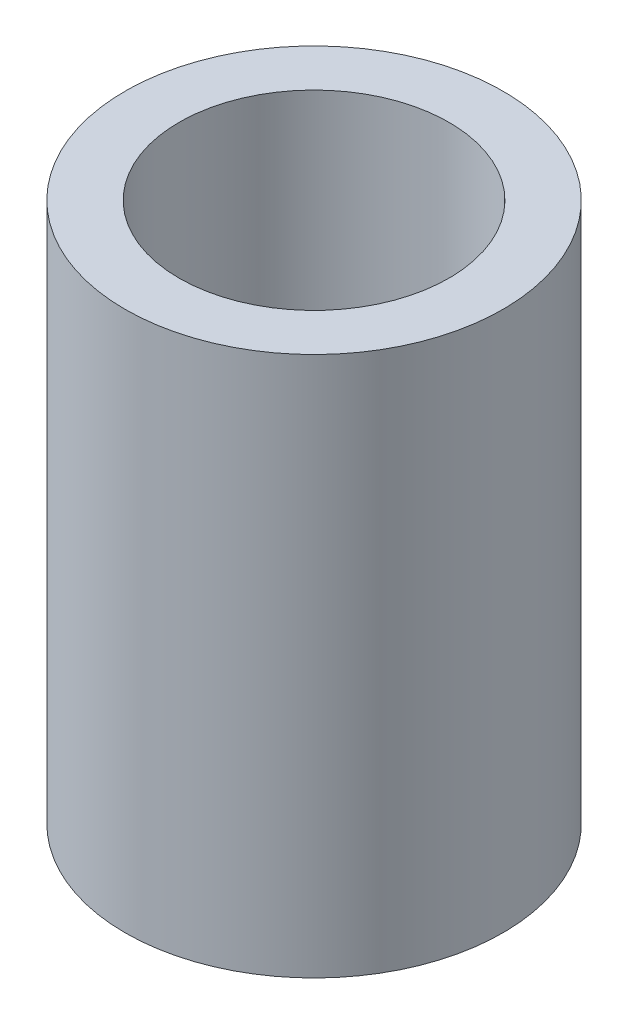
SolidWorks part; units mm, degrees
ref_plane "Front Plane" through (0, 0, 0) normal (0, 0, 1) x (1, 0, 0)
ref_plane "Top Plane" through (0, 0, 0) normal (0, 1, 0) x (1, 0, 0)
ref_plane "Right Plane" through (0, 0, 0) normal (1, 0, 0) x (0, 0, -1)
sketch "Sketch1" plane through (0, 0, 0) normal (0, 1, 0) x (1, 0, 0)
  circle A0 centre (0, 0) radius 10.5
  circle A1 centre (0, 0) radius 7.5
extrude "Boss-Extrude1" add sketch "Sketch1" along normal mid plane 30
ref_axis "Axis1" through (0, 15, 0) along (0, -1, 0)
